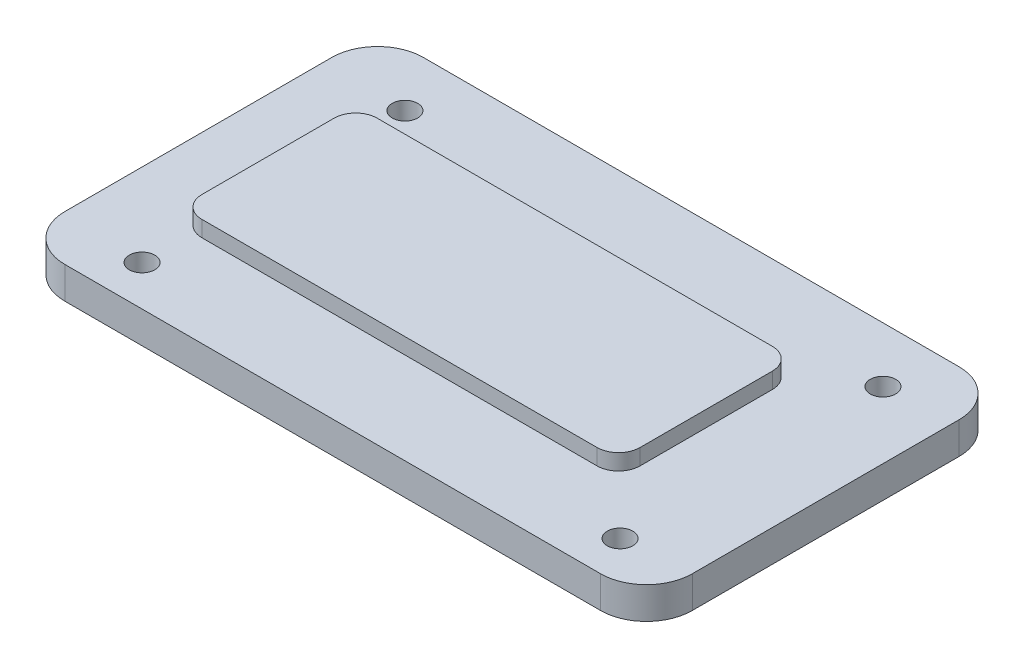
SolidWorks part; units mm, degrees
ref_plane "Front Plane" through (0, 0, 0) normal (0, 0, 1) x (1, 0, 0)
ref_plane "Top Plane" through (0, 0, 0) normal (0, 1, 0) x (1, 0, 0)
ref_plane "Right Plane" through (0, 0, 0) normal (1, 0, 0) x (0, 0, -1)
sketch "Sketch1" plane through (0, 0, 0) normal (0, 1, 0) x (1, 0, 0)
  line L0 (21.25, -8.375) -> (21.25, 8.375)
  line L1 (18.375, 11.25) -> (-15.25, 11.25)
  line L2 (-18.125, 8.375) -> (-18.125, -8.375)
  line L3 (-15.25, -11.25) -> (18.375, -11.25)
  line L4 (-15.25, -11.5) -> (18.375, -11.5)
  line L5 (-18.375, 8.375) -> (-18.375, -8.375)
  line L6 (18.375, 11.5) -> (-15.25, 11.5)
  line L7 (21.5, -8.375) -> (21.5, 8.375)
  line L8 (-15.25, -11.5) -> (18.375, -11.5) construction
  line L9 (-18.375, 8.375) -> (-18.375, -8.375) construction
  line L10 (18.375, 11.5) -> (-15.25, 11.5) construction
  line L11 (21.5, -8.375) -> (21.5, 8.375) construction
  arc A0 (21.25, 8.375) -> (18.375, 11.25) centre (18.375, 8.375) ccw
  arc A1 (-15.25, 11.25) -> (-18.125, 8.375) centre (-15.25, 8.375) ccw
  arc A2 (-18.125, -8.375) -> (-15.25, -11.25) centre (-15.25, -8.375) ccw
  arc A3 (18.375, -11.25) -> (21.25, -8.375) centre (18.375, -8.375) ccw
  arc A4 (-18.375, -8.375) -> (-15.25, -11.5) centre (-15.25, -8.375) ccw
  arc A5 (-15.25, 11.5) -> (-18.375, 8.375) centre (-15.25, 8.375) ccw
  arc A6 (21.5, 8.375) -> (18.375, 11.5) centre (18.375, 8.375) ccw
  arc A7 (18.375, -11.5) -> (21.5, -8.375) centre (18.375, -8.375) ccw
  arc A8 (-18.375, -8.375) -> (-15.25, -11.5) centre (-15.25, -8.375) ccw construction
  arc A9 (-15.25, 11.5) -> (-18.375, 8.375) centre (-15.25, 8.375) ccw construction
  arc A10 (21.5, 8.375) -> (18.375, 11.5) centre (18.375, 8.375) ccw construction
  arc A11 (18.375, -11.5) -> (21.5, -8.375) centre (18.375, -8.375) ccw construction
  dimension "D1" = 0
  dimension "D2" = 0.25
extrude "Boss-Extrude1" add sketch "Sketch1" along normal blind 3
sketch "Sketch2" plane through (0, 3, 0) normal (0, 1, 0) x (1, 0, 0)
  line L0 (14, -4.15) -> (14, 4.15) construction
  line L1 (12.4, 5.75) -> (-12.4, 5.75) construction
  line L2 (18.375, 11.5) -> (-15.25, 11.5) construction
  line L3 (24.5, 12.5) -> (-21.375, 12.5)
  line L4 (21.25, -8.375) -> (21.25, 8.375)
  line L5 (18.375, 11.25) -> (-15.25, 11.25)
  line L6 (-18.125, 8.375) -> (-18.125, -8.375)
  line L7 (-15.25, -11.25) -> (18.375, -11.25)
  line L8 (21.25, -8.375) -> (21.25, 8.375)
  line L9 (18.375, 11.25) -> (-15.25, 11.25)
  line L10 (-18.125, 8.375) -> (-18.125, -8.375)
  line L11 (-15.25, -11.25) -> (18.375, -11.25)
  line L12 (-24.5, 9.375) -> (-24.5, -9.375)
  line L13 (-21.375, -12.5) -> (24.5, -12.5)
  line L14 (24.5, 12.5) -> (-21.375, 12.5)
  line L15 (-24.5, 9.375) -> (-24.5, -9.375)
  line L16 (-21.375, -12.5) -> (24.5, -12.5)
  line L17 (-12.4, -5.75) -> (12.4, -5.75) construction
  line L18 (-14, 4.15) -> (-14, -4.15) construction
  line L19 (14, -4.15) -> (14, 4.15) construction
  line L20 (12.4, 5.75) -> (-12.4, 5.75) construction
  line L21 (18.375, 11.5) -> (-15.25, 11.5)
  line L22 (-12.4, -5.75) -> (12.4, -5.75) construction
  line L23 (-14, 4.15) -> (-14, -4.15) construction
  line L30 (-13.75, 4.15) -> (-13.75, -4.15)
  line L31 (-12.4, -5.5) -> (12.4, -5.5)
  line L32 (13.75, -4.15) -> (13.75, 4.15)
  line L33 (12.4, 5.5) -> (-12.4, 5.5)
  arc A0 (12.4, -5.75) -> (14, -4.15) centre (12.4, -4.15) ccw construction
  arc A1 (-12.4, 5.75) -> (-14, 4.15) centre (-12.4, 4.15) ccw construction
  arc A2 (14, 4.15) -> (12.4, 5.75) centre (12.4, 4.15) ccw construction
  arc A3 (-15.25, 11.5) -> (-18.375, 8.375) centre (-15.25, 8.375) ccw construction
  arc A4 (18.375, -11.25) -> (21.25, -8.375) centre (18.375, -8.375) ccw
  arc A5 (21.25, 8.375) -> (18.375, 11.25) centre (18.375, 8.375) ccw
  arc A6 (-15.25, 11.25) -> (-18.125, 8.375) centre (-15.25, 8.375) ccw
  arc A7 (-18.125, -8.375) -> (-15.25, -11.25) centre (-15.25, -8.375) ccw
  arc A8 (18.375, -11.25) -> (21.25, -8.375) centre (18.375, -8.375) ccw
  arc A9 (21.25, 8.375) -> (18.375, 11.25) centre (18.375, 8.375) ccw
  arc A10 (-15.25, 11.25) -> (-18.125, 8.375) centre (-15.25, 8.375) ccw
  arc A11 (-18.125, -8.375) -> (-15.25, -11.25) centre (-15.25, -8.375) ccw
  arc A12 (-14, -4.15) -> (-12.4, -5.75) centre (-12.4, -4.15) ccw construction
  arc A13 (-21.375, 12.5) -> (-24.5, 9.375) centre (-21.375, 9.375) ccw
  arc A14 (-24.5, -9.375) -> (-21.375, -12.5) centre (-21.375, -9.375) ccw
  arc A15 (24.5, -12.5) -> (27, -7.5) centre (24.5, -9.375) ccw
  arc A16 (27, 7.5) -> (27, -7.5) centre (37, 0) ccw
  arc A17 (27, 7.5) -> (24.5, 12.5) centre (24.5, 9.375) ccw
  arc A18 (-21.375, 12.5) -> (-24.5, 9.375) centre (-21.375, 9.375) ccw
  arc A19 (-24.5, -9.375) -> (-21.375, -12.5) centre (-21.375, -9.375) ccw
  arc A20 (24.5, -12.5) -> (27, -7.5) centre (24.5, -9.375) ccw
  arc A21 (27, 7.5) -> (27, -7.5) centre (37, 0) ccw
  arc A22 (27, 7.5) -> (24.5, 12.5) centre (24.5, 9.375) ccw
  arc A23 (12.4, -5.75) -> (14, -4.15) centre (12.4, -4.15) ccw construction
  arc A24 (-12.4, 5.75) -> (-14, 4.15) centre (-12.4, 4.15) ccw construction
  arc A25 (14, 4.15) -> (12.4, 5.75) centre (12.4, 4.15) ccw construction
  arc A26 (-15.25, 11.5) -> (-18.375, 8.375) centre (-15.25, 8.375) ccw
  arc A27 (-14, -4.15) -> (-12.4, -5.75) centre (-12.4, -4.15) ccw construction
  arc A38 (-13.75, -4.15) -> (-12.4, -5.5) centre (-12.4, -4.15) ccw
  arc A39 (12.4, -5.5) -> (13.75, -4.15) centre (12.4, -4.15) ccw
  arc A40 (13.75, 4.15) -> (12.4, 5.5) centre (12.4, 4.15) ccw
  arc A41 (-12.4, 5.5) -> (-13.75, 4.15) centre (-12.4, 4.15) ccw
  arc M25 (18.375, -11.25) -> (21.25, -8.375) centre (18.375, -8.375) ccw
  line M26 (21.25, -8.375) -> (21.25, 8.375)
  arc M27 (21.25, 8.375) -> (18.375, 11.25) centre (18.375, 8.375) ccw
  line M28 (18.375, 11.25) -> (-15.25, 11.25)
  arc M29 (-15.25, 11.25) -> (-18.125, 8.375) centre (-15.25, 8.375) ccw
  line M30 (-18.125, 8.375) -> (-18.125, -8.375)
  arc M31 (-18.125, -8.375) -> (-15.25, -11.25) centre (-15.25, -8.375) ccw
  line M32 (-15.25, -11.25) -> (18.375, -11.25)
  dimension "D1" = 0
  dimension "D2" = 0
  dimension "D3" = 0.25
extrude "Cut-Extrude1" cut sketch "Sketch2" against normal blind 1 contours A27 L23 A24 L20 A25 L19 A23 L22 M32 M25 M26 M27 M28 M29 M30 M31 region at (20.0873, 3, 10.0873)
sketch "Sketch3" plane through (0, 0, 0) normal (0, -1, 0) x (1, 0, 0)
  line L4 (18.375, 11.25) -> (-15.25, 11.25)
  line L5 (-18.125, 8.375) -> (-18.125, -8.375)
  line L6 (-15.25, -11.25) -> (18.375, -11.25)
  line L7 (21.25, -8.375) -> (21.25, 8.375)
  line L8 (18.375, 11.25) -> (-15.25, 11.25)
  line L9 (-18.125, 8.375) -> (-18.125, -8.375)
  line L10 (-15.25, -11.25) -> (18.375, -11.25)
  line L11 (21.25, -8.375) -> (21.25, 8.375)
  circle A0 centre (-12.9353, 8.721) radius 1.25 construction
  circle A1 centre (-12.9353, -7.779) radius 1.25 construction
  circle A2 centre (17.0647, -7.779) radius 1.25 construction
  circle A3 centre (17.0647, 8.721) radius 1.25 construction
  arc A4 (21.25, 8.375) -> (18.375, 11.25) centre (18.375, 8.375) ccw
  arc A5 (-15.25, 11.25) -> (-18.125, 8.375) centre (-15.25, 8.375) ccw
  arc A6 (-18.125, -8.375) -> (-15.25, -11.25) centre (-15.25, -8.375) ccw
  arc A7 (18.375, -11.25) -> (21.25, -8.375) centre (18.375, -8.375) ccw
  arc A8 (21.25, 8.375) -> (18.375, 11.25) centre (18.375, 8.375) ccw
  arc A9 (-15.25, 11.25) -> (-18.125, 8.375) centre (-15.25, 8.375) ccw
  arc A10 (-18.125, -8.375) -> (-15.25, -11.25) centre (-15.25, -8.375) ccw
  arc A11 (18.375, -11.25) -> (21.25, -8.375) centre (18.375, -8.375) ccw
  circle A12 centre (-12.9353, 8.721) radius 1.25 construction
  circle A13 centre (-12.9353, -7.779) radius 1.25 construction
  circle A14 centre (17.0647, -7.779) radius 1.25 construction
  circle A15 centre (17.0647, 8.721) radius 1.25 construction
  circle A16 centre (17.0647, -7.779) radius 0.8
  circle A17 centre (-12.9353, -7.779) radius 0.8
  circle A18 centre (-12.9353, 8.721) radius 0.8
  circle A19 centre (17.0647, 8.721) radius 0.8
  dimension "D2" = 1.6
  dimension "D3" = 1.6
  dimension "D4" = 1.6
  dimension "D5" = 1.6
  dimension "D1" = 0
extrude "Cut-Extrude2" cut sketch "Sketch3" against normal through all contours A17 | A18 | A16 | A19 | A16 | A19 | A17 region at (17.0647, 0, -7.779) region at (-12.9353, 0, -7.779) region at (-12.9353, 0, 8.721) region at (17.0647, 0, 8.721)
